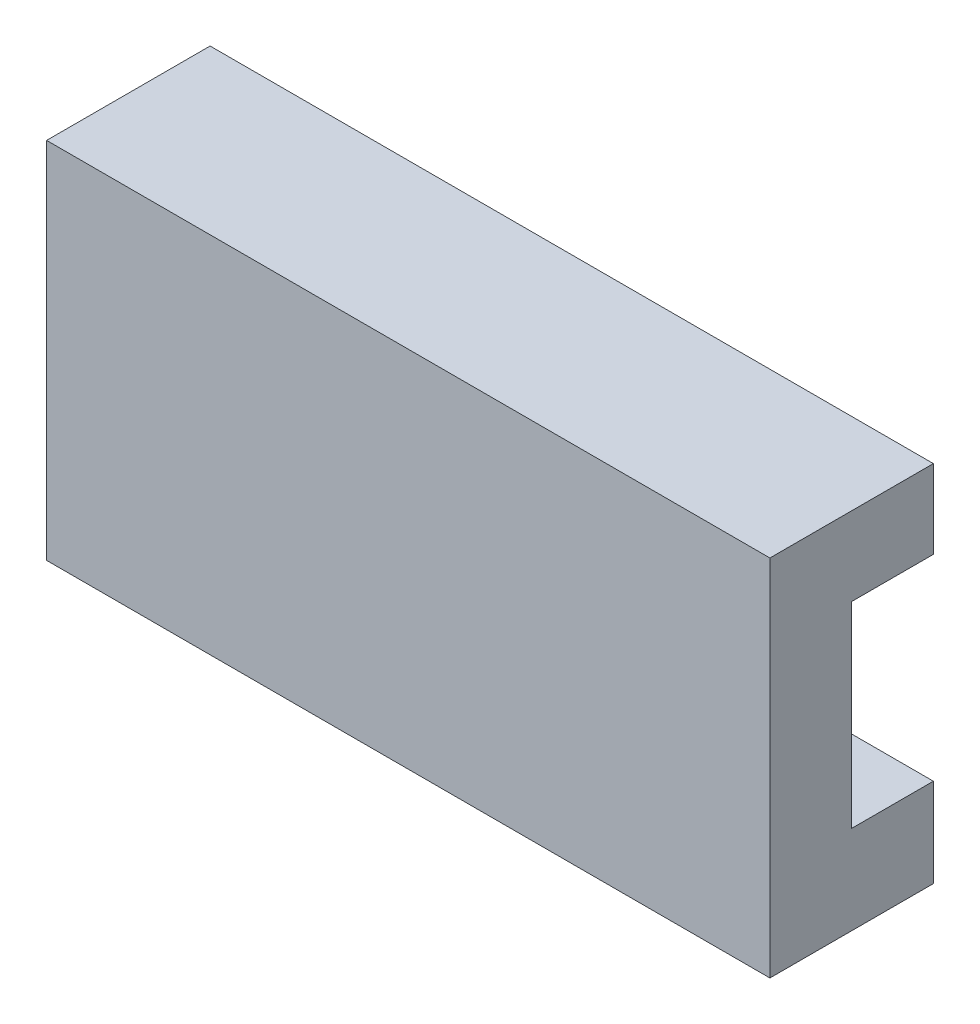
SolidWorks part; units mm, degrees
ref_plane "Front Plane" through (0, 0, 0) normal (0, 0, 1) x (1, 0, 0)
ref_plane "Top Plane" through (0, 0, 0) normal (0, 1, 0) x (1, 0, 0)
ref_plane "Right Plane" through (0, 0, 0) normal (1, 0, 0) x (0, 0, -1)
sketch "Sketch1" plane through (0, 0, 0) normal (0, 0, 1) x (1, 0, 0)
  line L0 (21.3, 7.75) -> (-21.3, 7.75) construction
  line L1 (-22.1208, 12.75) -> (22.1208, 12.75)
  line L2 (-22.1208, 12.75) -> (-22.1208, -9.5)
  line L3 (-22.1208, -9.5) -> (22.1208, -9.5)
  line L4 (22.1208, 12.75) -> (22.1208, -9.5)
  line L5 (-22.1208, 12.75) -> (22.1208, -9.5) construction
  line L6 (-22.1208, -9.5) -> (22.1208, 12.75) construction
  line L7 (-4.5, -4.5) -> (4.5, -4.5) construction
  point P0 (0, 1.625)
  dimension "D1" = 5
  dimension "D2" = 5
extrude "Boss-Extrude1" add sketch "Sketch1" along normal blind 10
sketch "Sketch2" plane through (0, 0, 0) normal (0, 0, 1) x (1, 0, 0)
  line L0 (22.1208, -9.5) -> (22.1208, 12.75) construction
  line L1 (-22.1208, -4.0745) -> (22.1208, -4.0745)
  line L2 (-22.1208, -4.0745) -> (-22.1208, 7.9415)
  line L3 (-22.1208, 7.9415) -> (22.1208, 7.9415)
  line L4 (22.1208, -4.0745) -> (22.1208, 7.9415)
  line L5 (-22.1208, -4.0745) -> (22.1208, 7.9415) construction
  line L6 (-22.1208, 7.9415) -> (22.1208, -4.0745) construction
  point P0 (0, 1.9335)
extrude "Cut-Extrude1" cut sketch "Sketch2" along normal blind 5
